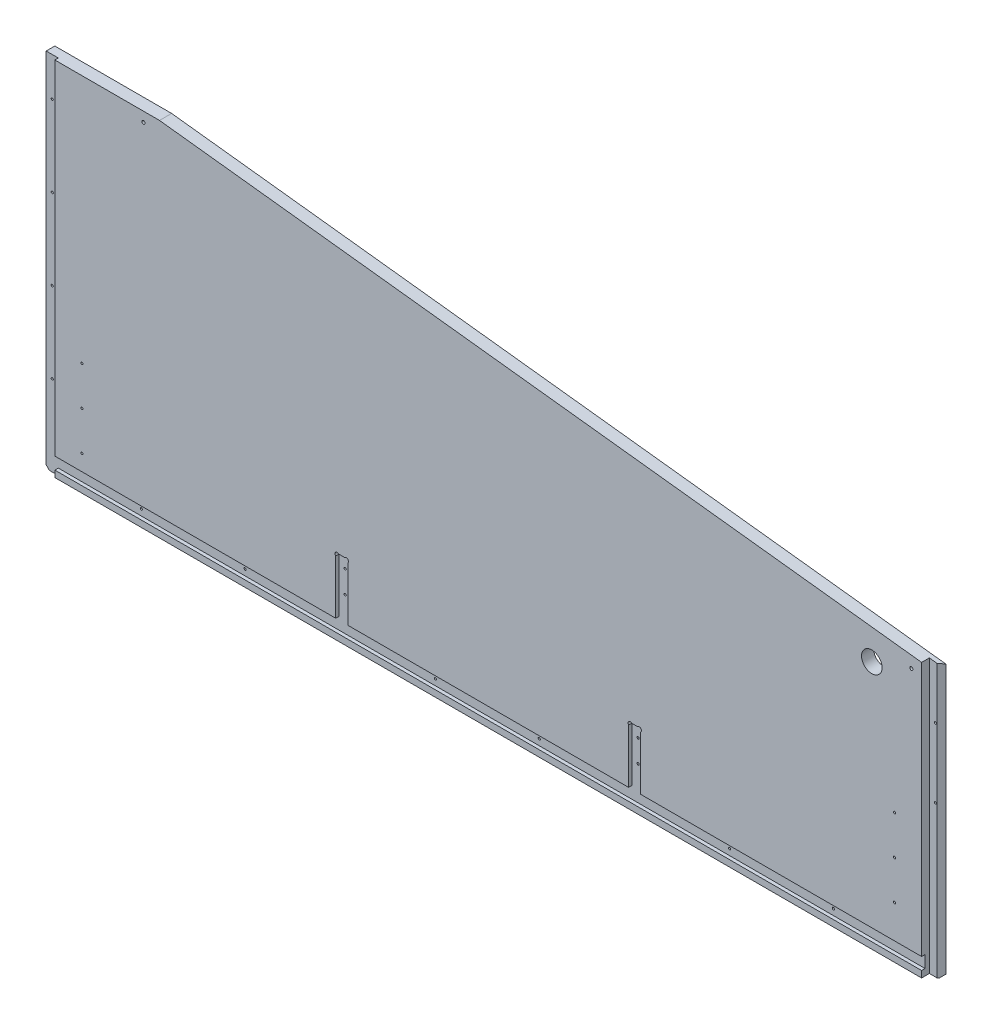
SolidWorks part; units mm, degrees
material "Pine"
ref_plane "Front Plane" through (0, 0, 0) normal (0, 0, 1) x (1, 0, 0)
ref_plane "Top Plane" through (0, 0, 0) normal (0, 1, 0) x (1, 0, 0)
ref_plane "Right Plane" through (0, 0, 0) normal (1, 0, 0) x (0, 0, -1)
sketch "Sketch1" plane through (0, 0, 0) normal (0, 0, 1) x (1, 0, 0)
  line L0 (8932.6508, -5243.5125) -> (10226.1458, -5243.5125)
  line L1 (9086.3208, -4722.0918) -> (10222.9708, -4853.7812)
  line L2 (8914.8708, -6342.0625) -> (10197.5708, -6342.0625)
  line L3 (8914.8708, -5808.6625) -> (10197.5708, -5808.6625)
  line L4 (8919.6333, -5253.0375) -> (10218.2083, -5253.0375)
  line L5 (9134.2633, -4656.1375) -> (9134.2633, -4638.3575)
  line L6 (9091.0833, -4638.3575) -> (9134.2633, -4638.3575)
  line L7 (9091.0833, -4567.2375) -> (9091.0833, -4638.3575)
  line L8 (9134.2633, -4656.1375) -> (9581.3033, -4656.1375)
  line L9 (9091.0833, -4567.2375) -> (9624.4833, -4567.2375)
  line L10 (9581.3033, -4656.1375) -> (9581.3033, -4638.3575)
  line L11 (9581.3033, -4638.3575) -> (9624.4833, -4638.3575)
  line L12 (9624.4833, -4567.2375) -> (9624.4833, -4638.3575)
  line L13 (8932.6508, -5225.7325) -> (9344.9775, -5225.7325)
  line L14 (8932.6508, -5256.2125) -> (8932.6508, -5243.5125)
  line L15 (8911.6958, -5256.2125) -> (8932.6508, -5256.2125)
  line L16 (8914.8708, -4722.0918) -> (9086.3208, -4722.0918)
  line L17 (8911.6958, -4715.5913) -> (8932.6508, -4715.5913)
  line L18 (8914.8708, -6342.0625) -> (8914.8708, -5808.6625)
  line L19 (12082.9917, -4722.0918) -> (10946.3417, -4853.7812)
  line L20 (12236.6617, -5243.5125) -> (10943.1667, -5243.5125)
  line L21 (10951.1042, -5253.0375) -> (12249.6792, -5253.0375)
  line L22 (10838.3917, -5656.2625) -> (11308.2917, -5656.2625)
  line L23 (10838.3917, -5719.7625) -> (11308.2917, -5719.7625)
  line L24 (10838.3917, -5742.5368) -> (11308.2917, -5742.5368)
  line L25 (10806.6417, -6342.0625) -> (11340.0417, -6342.0625)
  line L26 (10803.4667, -6335.7125) -> (11343.2167, -6335.7125)
  line L27 (10803.4667, -6317.9325) -> (11343.2167, -6317.9325)
  line L28 (10943.1667, -5225.7325) -> (11376.4483, -5225.7325)
  line L29 (11506.7292, -4754.5625) -> (10806.6417, -4827.5875)
  line L30 (11506.7292, -4567.2375) -> (11506.7292, -4754.5625)
  line L31 (10806.6417, -4567.2375) -> (10806.6417, -4827.5875)
  line L32 (10806.6417, -4567.2375) -> (11506.7292, -4567.2375)
  line L33 (10235.6708, -6329.3625) -> (10245.1958, -6329.3625)
  line L34 (10245.1958, -6329.3625) -> (10254.7208, -6278.5625)
  line L35 (10302.3458, -6329.3625) -> (10311.8708, -6278.5625)
  line L36 (10302.3458, -6329.3625) -> (10292.8208, -6329.3625)
  line L37 (10245.1958, -5821.3625) -> (10254.7208, -5872.1625)
  line L38 (10235.6708, -5821.3625) -> (10245.1958, -5821.3625)
  line L39 (10292.8208, -5821.3625) -> (10302.3458, -5821.3625)
  line L40 (10302.3458, -5821.3625) -> (10311.8708, -5872.1625)
  line L41 (10235.6708, -5821.3625) -> (10235.6708, -6329.3625)
  line L42 (10254.7208, -5872.1625) -> (10254.7208, -6278.5625)
  line L43 (10311.8708, -5872.1625) -> (10311.8708, -6278.5625)
  line L44 (10292.8208, -5821.3625) -> (10292.8208, -6329.3625)
  line L45 (8932.6508, -5225.7325) -> (8932.6508, -4715.5913)
  line L46 (8911.6958, -4715.5913) -> (8911.6958, -5256.2125)
  line L47 (8914.8708, -5248.275) -> (8914.8708, -4722.0918)
  line L48 (8919.6333, -5253.0375) -> (8914.8708, -5248.275)
  line L49 (8914.8708, -5145.0875) -> (8937.426, -5145.0875)
  line L50 (8914.8708, -5202.2375) -> (8937.426, -5202.2375)
  line L51 (10838.3917, -5656.2625) -> (10838.3917, -5719.7625)
  line L52 (10832.0417, -5736.1868) -> (10856.1717, -5736.1868)
  line L53 (10806.6417, -6342.0625) -> (10806.6417, -5818.7368)
  line L54 (10832.0417, -5649.9125) -> (10856.1717, -5649.9125)
  line L55 (10832.0417, -5726.1125) -> (10856.1717, -5726.1125)
  line L56 (10806.6417, -5818.7368) -> (10833.9015, -5818.7368)
  line L57 (10832.0417, -5806.0442) -> (10851.6815, -5806.0442)
  line L58 (10856.1717, -5801.5541) -> (10856.1717, -5736.1868)
  line L59 (10838.3917, -5814.2467) -> (10838.3917, -5742.5368)
  line L60 (10832.0417, -5806.0442) -> (10832.0417, -5736.1868)
  line L61 (10803.4667, -6317.9325) -> (10803.4667, -6335.7125)
  line L62 (10197.5708, -5808.6625) -> (10197.5708, -6342.0625)
  line L63 (9762.3842, -6348.4125) -> (9762.3842, -5802.3125)
  line L64 (9780.1642, -6348.4125) -> (9762.3842, -6348.4125)
  line L65 (9780.1642, -5802.3125) -> (9780.1642, -6348.4125)
  line L66 (9762.3842, -5802.3125) -> (9780.1642, -5802.3125)
  line L67 (9332.2775, -6348.4125) -> (9332.2775, -5802.3125)
  line L68 (9332.2775, -6348.4125) -> (9350.0575, -6348.4125)
  line L69 (9350.0575, -5802.3125) -> (9350.0575, -6348.4125)
  line L70 (9332.2775, -5802.3125) -> (9350.0575, -5802.3125)
  line L71 (9993.8374, -6061.075) -> (9993.8374, -6045.2418)
  line L72 (9998.5999, -6065.8375) -> (10014.4331, -6065.8375)
  line L73 (9998.5999, -6084.8875) -> (10014.4331, -6084.8875)
  line L74 (9993.8374, -6105.4832) -> (9993.8374, -6089.65)
  line L75 (9974.7874, -6105.4832) -> (9974.7874, -6089.65)
  line L76 (9954.1917, -6084.8875) -> (9970.0249, -6084.8875)
  line L77 (9974.7874, -6061.075) -> (9974.7874, -6045.2418)
  line L78 (9954.1917, -6065.8375) -> (9970.0249, -6065.8375)
  line L79 (10793.9417, -6237.2875) -> (10816.4969, -6237.2875)
  line L80 (10793.9417, -6294.4375) -> (10816.4969, -6294.4375)
  line L81 (10856.1717, -5649.9125) -> (10856.1717, -5726.1125)
  line L82 (10832.0417, -5726.1125) -> (10832.0417, -5649.9125)
  line L83 (10226.1458, -5225.7325) -> (10226.1458, -5243.5125)
  line L84 (10205.1908, -5257.8) -> (10205.1908, -4844.2499)
  line L85 (10230.9083, -4844.2499) -> (10230.9083, -5257.8)
  line L86 (10205.1908, -5257.8) -> (10230.9083, -5257.8)
  line L87 (10205.1908, -4844.2499) -> (10230.9083, -4844.2499)
  line L88 (10946.3417, -5176.8375) -> (10968.8969, -5176.8375)
  line L89 (9349.4676, -5141.9125) -> (9358.2674, -5141.9125)
  line L90 (10946.3417, -5119.6875) -> (10968.8969, -5119.6875)
  line L91 (9929.011, -4660.9635) -> (10066.0807, -4660.9635)
  line L92 (9929.011, -4678.7435) -> (10066.0807, -4678.7435)
  line L93 (10943.1667, -5225.7325) -> (10943.1667, -5243.5125)
  line L94 (10946.3417, -5248.275) -> (10951.1042, -5253.0375)
  line L95 (10946.3417, -5257.8063) -> (10946.3417, -4849.0188)
  line L96 (10964.1217, -5257.8) -> (10964.1217, -4844.2499)
  line L97 (10938.4042, -4844.2499) -> (10938.4042, -5257.8)
  line L98 (10938.4042, -5257.8) -> (10964.1217, -5257.8)
  line L99 (10964.1217, -4844.2499) -> (10938.4042, -4844.2499)
  line L100 (10344.8908, -4560.8875) -> (10369.0208, -4560.8875)
  line L101 (10344.8908, -4560.8875) -> (10369.0208, -4560.8875)
  line L102 (10800.2917, -4560.8875) -> (10824.4217, -4560.8875)
  line L103 (10200.4156, -5119.6875) -> (10222.9708, -5119.6875)
  line L104 (10200.4156, -5176.8375) -> (10222.9708, -5176.8375)
  line L105 (9344.9775, -5146.4026) -> (9344.9775, -5225.7325)
  line L106 (10344.8908, -4560.8875) -> (10344.8908, -4833.9375)
  line L107 (9792.8642, -5225.7325) -> (9792.8642, -5146.4026)
  line L108 (9362.7575, -5225.7325) -> (9775.0842, -5225.7325)
  line L109 (9680.3633, -4761.8396) -> (9680.3633, -4559.9604)
  line L110 (9656.2333, -4559.9604) -> (9680.3633, -4559.9604)
  line L111 (9656.2333, -4761.8396) -> (9680.3633, -4761.8396)
  line L112 (9656.2333, -4761.8396) -> (9656.2333, -4559.9604)
  line L113 (9779.5743, -5141.9125) -> (9788.374, -5141.9125)
  line L114 (10070.5708, -4665.4536) -> (10070.5708, -4674.2534)
  line L115 (9924.5208, -4674.2534) -> (9924.5208, -4665.4536)
  line L116 (12127.4417, -6188.3925) -> (12205.5015, -6188.3925)
  line L117 (12209.9917, -6170.6125) -> (12209.9917, -6183.9024)
  line L118 (9792.8642, -5225.7325) -> (10226.1458, -5225.7325)
  line L119 (9662.5833, -4754.5625) -> (10362.6708, -4827.5875)
  line L120 (9662.5833, -4567.2375) -> (9662.5833, -4754.5625)
  line L121 (10362.6708, -4567.2375) -> (10362.6708, -4827.5875)
  line L122 (9662.5833, -4567.2375) -> (10362.6708, -4567.2375)
  line L123 (10824.4217, -4833.9375) -> (10800.2917, -4833.9375)
  line L124 (10800.2917, -4833.9375) -> (10800.2917, -4560.8875)
  line L125 (10824.4217, -4560.8875) -> (10824.4217, -4833.9375)
  line L126 (10344.8908, -4833.9375) -> (10369.0208, -4833.9375)
  line L127 (10369.0208, -4833.9375) -> (10369.0208, -4560.8875)
  line L128 (10222.9708, -5248.275) -> (10218.2083, -5253.0375)
  line L129 (10222.9708, -5257.8063) -> (10222.9708, -4849.0188)
  line L130 (11734.6544, -5701.375) -> (11739.2301, -5701.375)
  line L131 (9362.7575, -5225.7325) -> (9362.7575, -5146.4026)
  line L132 (9775.0842, -5146.4026) -> (9775.0842, -5225.7325)
  line L133 (11761.3864, -5701.375) -> (11756.8282, -5701.375)
  line L134 (11734.6544, -5693.755) -> (11739.2301, -5693.755)
  line L135 (11761.4039, -5693.755) -> (11756.8282, -5693.755)
  line L136 (11734.6544, -5701.375) -> (11739.2301, -5701.375)
  line L137 (11744.3462, -5721.3024) -> (11744.3462, -5706.4179)
  line L138 (11751.7122, -5721.3024) -> (11751.7122, -5706.4179)
  line L139 (11740.0917, -6170.6125) -> (11740.0917, -6183.9024)
  line L140 (11689.2917, -6188.3925) -> (11822.6417, -6188.3925)
  line L141 (11689.2917, -6348.4093) -> (11689.2917, -6164.2657)
  line L142 (11689.2917, -6164.2657) -> (11746.4417, -6164.2657)
  line L143 (11746.4417, -6164.2657) -> (11746.4417, -6188.3925)
  line L144 (11689.2917, -6164.2657) -> (11746.4417, -6164.2657)
  line L145 (11340.0417, -5818.7368) -> (11340.0417, -6342.0625)
  line L146 (11290.5117, -5726.1125) -> (11314.6417, -5726.1125)
  line L147 (11290.5117, -5649.9125) -> (11290.5117, -5726.1125)
  line L148 (11340.0417, -5818.7368) -> (11312.7818, -5818.7368)
  line L149 (11314.6417, -5806.0442) -> (11295.0018, -5806.0442)
  line L150 (11290.5117, -5801.5541) -> (11290.5117, -5736.1868)
  line L151 (11308.2917, -5814.2467) -> (11308.2917, -5742.5368)
  line L152 (11314.6417, -5806.0442) -> (11314.6417, -5736.1868)
  line L153 (11290.5117, -5736.1868) -> (11314.6417, -5736.1868)
  line L154 (11848.0417, -6267.1325) -> (11962.3417, -6267.1325)
  line L155 (11962.3417, -6267.1325) -> (11962.3417, -6203.6325)
  line L156 (11343.2167, -6317.9325) -> (11343.2167, -6335.7125)
  line L157 (11365.4417, -5656.2625) -> (11365.4417, -5719.7625)
  line L158 (11365.4417, -5656.2625) -> (11479.7417, -5656.2625)
  line L159 (11778.1917, -6071.3937) -> (11802.3217, -6071.3937)
  line L160 (11314.6417, -5726.1125) -> (11314.6417, -5649.9125)
  line L161 (11314.6417, -5649.9125) -> (11290.5117, -5649.9125)
  line L162 (11308.2917, -5719.7625) -> (11308.2917, -5656.2625)
  line L163 (11689.2917, -6348.4093) -> (11713.4217, -6348.4093)
  line L164 (12203.6417, -6164.2657) -> (12260.7917, -6164.2657)
  line L165 (11713.4217, -6348.4093) -> (11713.4217, -6164.2657)
  line L166 (11695.6417, -6342.0625) -> (11695.6417, -6170.6125)
  line L167 (11695.6417, -6048.5337) -> (11699.4517, -6052.3437)
  line L168 (11822.6417, -6292.5325) -> (11822.6417, -6188.3925)
  line L169 (11695.6417, -6342.0625) -> (11695.6417, -6170.6125)
  line L170 (11848.0417, -6203.6325) -> (11962.3417, -6203.6325)
  line L171 (11848.0417, -6203.6325) -> (11848.0417, -6267.1325)
  line L172 (11987.7417, -6267.1325) -> (11987.7417, -6203.6325)
  line L173 (11784.5417, -6077.7437) -> (11784.5417, -6141.2438)
  line L174 (11517.8417, -5656.2625) -> (11632.1417, -5656.2625)
  line L175 (11632.1417, -5656.2625) -> (11632.1417, -5719.7625)
  line L176 (11632.1417, -5719.7625) -> (11517.8417, -5719.7625)
  line L177 (11517.8417, -5719.7625) -> (11517.8417, -5656.2625)
  line L178 (11692.4667, -6028.2137) -> (11692.4667, -6045.9937)
  line L179 (11695.6417, -5979.3188) -> (11718.1969, -5979.3188)
  line L180 (11695.6417, -5922.1687) -> (11718.1969, -5922.1687)
  line L181 (11821.0415, -5722.9375) -> (11821.0415, -5943.6)
  line L182 (11687.7042, -5651.5) -> (11701.9917, -5651.5)
  line L183 (11687.7042, -5651.5) -> (11687.7042, -6055.5251)
  line L184 (11687.7042, -6055.5251) -> (11701.9917, -6055.5251)
  line L185 (11701.9917, -6055.5251) -> (11701.9917, -5651.5)
  line L186 (11695.6417, -6055.2013) -> (11695.6417, -5649.595)
  line L187 (11695.6417, -5656.2625) -> (11695.6417, -6048.5337)
  line L188 (11695.6417, -6170.6125) -> (11740.0917, -6170.6125)
  line L189 (12203.6417, -6164.2657) -> (12203.6417, -6188.3925)
  line L190 (12254.4417, -6342.0625) -> (12254.4417, -6170.6125)
  line L191 (12129.0419, -5943.6) -> (12129.0419, -5722.9375)
  line L192 (12254.4417, -6048.5337) -> (12250.6317, -6052.3437)
  line L193 (12257.6167, -6045.9937) -> (12257.6167, -6028.2137)
  line L194 (12248.0917, -5651.5) -> (12262.3792, -5651.5)
  line L195 (12262.3792, -5651.5) -> (12262.3792, -6055.5251)
  line L196 (12262.3792, -6055.5251) -> (12248.0917, -6055.5251)
  line L197 (12248.0917, -6055.5251) -> (12248.0917, -5651.5)
  line L198 (12254.4417, -6141.2438) -> (12254.4417, -6077.7437)
  line L199 (12236.6617, -6164.2657) -> (12260.7917, -6164.2657)
  line L200 (12102.0417, -6267.1325) -> (11987.7417, -6267.1325)
  line L201 (11330.1865, -6237.2875) -> (11352.7417, -6237.2875)
  line L202 (11330.1865, -6294.4375) -> (11352.7417, -6294.4375)
  line L203 (11474.6617, -5851.8425) -> (11492.4417, -5851.8425)
  line L204 (11474.6617, -5808.6625) -> (11474.6617, -5851.8425)
  line L205 (11403.5417, -5808.6625) -> (11474.6617, -5808.6625)
  line L206 (11492.4417, -5851.8425) -> (11492.4417, -6298.8825)
  line L207 (11403.5417, -6342.0625) -> (11403.5417, -5808.6625)
  line L208 (11474.6617, -6298.8825) -> (11492.4417, -6298.8825)
  line L209 (11474.6617, -6342.0625) -> (11474.6617, -6298.8825)
  line L210 (11403.5417, -6342.0625) -> (11474.6617, -6342.0625)
  line L211 (11619.4417, -5851.8425) -> (11601.6617, -5851.8425)
  line L212 (11601.6617, -5808.6625) -> (11601.6617, -5851.8425)
  line L213 (11530.5417, -5808.6625) -> (11601.6617, -5808.6625)
  line L214 (11619.4417, -5851.8425) -> (11619.4417, -6298.8825)
  line L215 (11530.5417, -6342.0625) -> (11530.5417, -5808.6625)
  line L216 (11619.4417, -6298.8825) -> (11601.6617, -6298.8825)
  line L217 (11601.6617, -6342.0625) -> (11601.6617, -6298.8825)
  line L218 (11530.5417, -6342.0625) -> (11601.6617, -6342.0625)
  line L219 (11479.7417, -5719.7625) -> (11479.7417, -5656.2625)
  line L220 (11365.4417, -5719.7625) -> (11479.7417, -5719.7625)
  line L221 (11778.1917, -6147.5937) -> (11802.3217, -6147.5937)
  line L222 (11802.3217, -6071.3937) -> (11802.3217, -6147.5937)
  line L223 (11778.1917, -6147.5937) -> (11778.1917, -6071.3937)
  line L224 (12254.4417, -5922.1687) -> (12231.8865, -5922.1687)
  line L225 (12254.4417, -5979.3188) -> (12231.8865, -5979.3188)
  line L226 (12254.4417, -6055.2013) -> (12254.4417, -5649.595)
  line L227 (12254.4417, -6048.5337) -> (12254.4417, -5656.2625)
  line L228 (11841.6917, -5702.2873) -> (12108.3917, -5702.2873)
  line L229 (11822.6417, -6292.5325) -> (12127.4417, -6292.5325)
  line L230 (12127.4417, -6292.5325) -> (12127.4417, -6188.3925)
  line L231 (12254.4417, -6170.6125) -> (12209.9917, -6170.6125)
  line L232 (11695.6417, -6342.0625) -> (12254.4417, -6342.0625)
  line L233 (12236.6617, -6348.4093) -> (12260.7917, -6348.4093)
  line L234 (12260.7917, -6348.4093) -> (12260.7917, -6164.2657)
  line L235 (12236.6617, -6348.4093) -> (12236.6617, -6164.2657)
  line L236 (12102.0417, -6203.6325) -> (12102.0417, -6267.1325)
  line L237 (11987.7417, -6203.6325) -> (12102.0417, -6203.6325)
  line L238 (12236.6617, -6147.5937) -> (12236.6617, -6071.3937)
  line L239 (12203.6417, -6188.3925) -> (12260.7917, -6188.3925)
  line L240 (11098.7417, -4665.4536) -> (11098.7417, -4674.2534)
  line L241 (11394.2283, -5146.4026) -> (11394.2283, -5225.7325)
  line L242 (11376.4483, -5225.7325) -> (11376.4483, -5146.4026)
  line L243 (11394.2283, -5225.7325) -> (11806.555, -5225.7325)
  line L244 (11841.6917, -5964.2502) -> (12108.3917, -5964.2502)
  line L245 (12236.6617, -6147.5937) -> (12260.7917, -6147.5937)
  line L246 (12236.6617, -5256.2125) -> (12236.6617, -5243.5125)
  line L247 (12260.7917, -6147.5937) -> (12260.7917, -6071.3937)
  line L248 (12260.7917, -6071.3937) -> (12236.6617, -6071.3937)
  line L249 (12254.4417, -6077.7437) -> (11784.5417, -6077.7437)
  line L250 (11784.5417, -6141.2438) -> (12254.4417, -6141.2438)
  line L252 (12254.4417, -5656.2625) -> (11695.6417, -5656.2625)
  line L253 (11699.4517, -6052.3437) -> (12250.6317, -6052.3437)
  line L254 (11692.4667, -6045.9937) -> (12257.6167, -6045.9937)
  line L255 (11692.4667, -6028.2137) -> (12257.6167, -6028.2137)
  line L256 (11824.335, -5146.4026) -> (11824.335, -5225.7325)
  line L257 (11811.0451, -5141.9125) -> (11819.8449, -5141.9125)
  line L258 (11244.7917, -4674.2534) -> (11244.7917, -4665.4536)
  line L259 (11806.555, -5225.7325) -> (11806.555, -5146.4026)
  line L260 (11488.9492, -4761.8396) -> (11488.9492, -4559.9604)
  line L261 (11488.9492, -4559.9604) -> (11513.0792, -4559.9604)
  line L262 (11488.9492, -4761.8396) -> (11513.0792, -4761.8396)
  line L263 (11513.0792, -4761.8396) -> (11513.0792, -4559.9604)
  line L264 (11240.3015, -4660.9635) -> (11103.2318, -4660.9635)
  line L265 (11103.2318, -4678.7435) -> (11240.3015, -4678.7435)
  line L266 (12236.6617, -5225.7325) -> (12236.6617, -4715.5913)
  line L267 (12257.6167, -4715.5913) -> (12257.6167, -5256.2125)
  line L268 (12254.4417, -5248.275) -> (12254.4417, -4722.0918)
  line L269 (12236.6617, -5225.7325) -> (11824.335, -5225.7325)
  line L270 (12035.0492, -4656.1375) -> (12035.0492, -4638.3575)
  line L271 (12078.2292, -4638.3575) -> (12035.0492, -4638.3575)
  line L272 (12078.2292, -4567.2375) -> (12078.2292, -4638.3575)
  line L273 (12035.0492, -4656.1375) -> (11588.0092, -4656.1375)
  line L274 (11544.8292, -4567.2375) -> (12078.2292, -4567.2375)
  line L275 (11588.0092, -4656.1375) -> (11588.0092, -4638.3575)
  line L276 (11544.8292, -4638.3575) -> (11588.0092, -4638.3575)
  line L277 (11544.8292, -4567.2375) -> (11544.8292, -4638.3575)
  line L278 (12249.6792, -5253.0375) -> (12254.4417, -5248.275)
  line L280 (12257.6167, -5256.2125) -> (12236.6617, -5256.2125)
  line L281 (12231.8865, -5145.0875) -> (12254.4417, -5145.0875)
  line L282 (12231.8865, -5202.2375) -> (12254.4417, -5202.2375)
  line L283 (12236.6617, -4715.5913) -> (12257.6167, -4715.5913)
  line L284 (12082.9917, -4722.0918) -> (12254.4417, -4722.0918)
  line L285 (11380.9385, -5141.9125) -> (11389.7382, -5141.9125)
  circle A0 centre (8923.7608, -4778.9042) radius 1.5875
  circle A1 centre (9062.6598, -4736.3765) radius 2.3685
  circle A2 centre (9051.3958, -6281.7375) radius 22.225
  circle A3 centre (9083.1458, -6249.9875) radius 1.5875
  circle A4 centre (9083.1458, -6313.4875) radius 1.5875
  circle A5 centre (9019.6458, -6249.9875) radius 1.5875
  circle A6 centre (9019.6458, -6313.4875) radius 1.5875
  circle A7 centre (8972.3383, -5202.2375) radius 1.5875
  circle A8 centre (8923.7608, -5015.9708) radius 1.5875
  circle A9 centre (8923.7608, -5134.5042) radius 1.5875
  circle A10 centre (9054.5708, -5234.6225) radius 1.5875
  circle A11 centre (8923.7608, -4897.4375) radius 1.5875
  circle A12 centre (8972.3383, -5087.9375) radius 1.5875
  circle A13 centre (8972.3383, -5145.0875) radius 1.5875
  circle A14 centre (10847.2817, -5668.9625) radius 1.5875
  circle A15 centre (10847.2817, -5707.0625) radius 1.5875
  circle A16 centre (10847.2817, -5755.2368) radius 1.5875
  circle A17 centre (10851.4092, -6237.2875) radius 1.5875
  circle A18 centre (10851.4092, -6294.4375) radius 1.5875
  circle A19 centre (10847.2817, -5793.3442) radius 1.5875
  arc A20 (10833.9015, -5818.7368) -> (10838.3917, -5814.2467) centre (10836.1466, -5816.4918) ccw
  arc A21 (10851.6815, -5806.0442) -> (10856.1717, -5801.5541) centre (10853.9266, -5803.7992) ccw
  circle A22 centre (10882.8417, -6040.4375) radius 1.5875
  circle A23 centre (10882.8417, -6218.2375) radius 1.5875
  circle A24 centre (10882.8417, -5862.6375) radius 1.5875
  circle A25 centre (10908.2417, -6326.8225) radius 1.5875
  circle A26 centre (10908.2417, -6326.8225) radius 1.5875
  circle A27 centre (10851.4092, -6180.1375) radius 1.5875
  circle A28 centre (10815.5317, -4783.4231) radius 1.5875
  circle A29 centre (10815.5317, -4696.9488) radius 1.5875
  circle A30 centre (10815.5317, -4610.4746) radius 1.5875
  circle A31 centre (10979.1323, -4867.0082) radius 2.3685
  circle A32 centre (10190.1802, -4867.0082) radius 2.3685
  circle A33 centre (10955.2317, -4929.9812) radius 1.5875
  circle A34 centre (10955.2317, -5031.5812) radius 1.5875
  circle A35 centre (10214.0808, -4929.9812) radius 1.5875
  circle A36 centre (10214.0808, -5031.5812) radius 1.5875
  circle A37 centre (9341.1675, -6265.8625) radius 1.5875
  circle A38 centre (9771.2742, -5884.8625) radius 1.5875
  circle A39 centre (9771.2742, -6138.8625) radius 1.5875
  circle A40 centre (9771.2742, -6011.8625) radius 1.5875
  arc A41 (10036.2287, -6113.8083) -> (10051.3426, -6111.6033) centre (10042.9639, -6107.0732) ccw
  arc A42 (10051.3426, -6111.6033) -> (10051.3426, -6039.1217) centre (9984.3124, -6075.3625) ccw
  arc A43 (10051.3426, -6039.1217) -> (10036.2287, -6036.9167) centre (10042.9639, -6043.6518) ccw
  arc A44 (10034.5851, -6102.5431) -> (10034.5851, -6048.1819) centre (9984.3124, -6075.3625) ccw
  arc A45 (10034.5851, -6102.5431) -> (10036.2287, -6113.8083) centre (10042.9639, -6107.0732) ccw
  arc A46 (10036.2287, -6036.9167) -> (10034.5851, -6048.1819) centre (10042.9639, -6043.6518) ccw
  arc A47 (9945.8666, -6127.2787) -> (9948.0717, -6142.3927) centre (9952.6018, -6134.0139) ccw
  arc A48 (9948.0717, -6142.3927) -> (10020.5532, -6142.3927) centre (9984.3124, -6075.3625) ccw
  arc A49 (10020.5532, -6142.3927) -> (10022.7583, -6127.2787) centre (10016.0231, -6134.0139) ccw
  arc A50 (9957.1319, -6125.6352) -> (10011.493, -6125.6352) centre (9984.3124, -6075.3625) ccw
  arc A51 (9957.1319, -6125.6352) -> (9945.8666, -6127.2787) centre (9952.6018, -6134.0139) ccw
  arc A52 (10022.7583, -6127.2787) -> (10011.493, -6125.6352) centre (10016.0231, -6134.0139) ccw
  arc A53 (9932.3962, -6036.9167) -> (9917.2822, -6039.1217) centre (9925.661, -6043.6518) ccw
  arc A54 (9917.2822, -6039.1217) -> (9917.2822, -6111.6033) centre (9984.3124, -6075.3625) ccw
  arc A55 (9917.2822, -6111.6033) -> (9932.3962, -6113.8083) centre (9925.661, -6107.0732) ccw
  arc A56 (9934.0398, -6048.1819) -> (9934.0398, -6102.5431) centre (9984.3124, -6075.3625) ccw
  arc A57 (9934.0398, -6048.1819) -> (9932.3962, -6036.9167) centre (9925.661, -6043.6518) ccw
  arc A58 (9932.3962, -6113.8083) -> (9934.0398, -6102.5431) centre (9925.661, -6107.0732) ccw
  arc A59 (9945.8666, -6023.4463) -> (9957.1319, -6025.0898) centre (9952.6018, -6016.7111) ccw
  arc A60 (10011.493, -6025.0898) -> (10022.7583, -6023.4463) centre (10016.0231, -6016.7111) ccw
  arc A61 (10011.493, -6025.0898) -> (9957.1319, -6025.0898) centre (9984.3124, -6075.3625) ccw
  arc A62 (9948.0717, -6008.3323) -> (9945.8666, -6023.4463) centre (9952.6018, -6016.7111) ccw
  arc A63 (10020.5532, -6008.3323) -> (9948.0717, -6008.3323) centre (9984.3124, -6075.3625) ccw
  arc A64 (10022.7583, -6023.4463) -> (10020.5532, -6008.3323) centre (10016.0231, -6016.7111) ccw
  arc A65 (10005.0943, -6187.7574) -> (10096.7073, -6096.1443) centre (9984.3124, -6075.3625) ccw
  arc A66 (9993.8374, -6178.3911) -> (10005.0943, -6187.7574) centre (10003.3624, -6178.3911) ccw
  arc A67 (10001.6306, -6169.0249) -> (10077.9748, -6092.6807) centre (9984.3124, -6075.3625) ccw
  arc A68 (10087.3411, -6084.8875) -> (10077.9748, -6092.6807) centre (10087.3411, -6094.4125) ccw
  arc A69 (10001.6306, -6169.0249) -> (9993.8374, -6178.3911) centre (10003.3624, -6178.3911) ccw
  arc A70 (9963.5306, -6187.7574) -> (9974.7874, -6178.3911) centre (9965.2624, -6178.3911) ccw
  arc A71 (9871.9176, -6096.1443) -> (9963.5306, -6187.7574) centre (9984.3124, -6075.3625) ccw
  arc A72 (9881.2838, -6084.8875) -> (9871.9176, -6096.1443) centre (9881.2838, -6094.4125) ccw
  arc A73 (9890.65, -6092.6807) -> (9966.9943, -6169.0249) centre (9984.3124, -6075.3625) ccw
  arc A74 (9974.7874, -6178.3911) -> (9966.9943, -6169.0249) centre (9965.2624, -6178.3911) ccw
  arc A75 (9890.65, -6092.6807) -> (9881.2838, -6084.8875) centre (9881.2838, -6094.4125) ccw
  arc A76 (9871.9176, -6054.5807) -> (9881.2838, -6065.8375) centre (9881.2838, -6056.3125) ccw
  arc A77 (9963.5306, -5962.9676) -> (9871.9176, -6054.5807) centre (9984.3124, -6075.3625) ccw
  arc A78 (9974.7874, -5972.3339) -> (9963.5306, -5962.9676) centre (9965.2624, -5972.3339) ccw
  arc A79 (9966.9943, -5981.7001) -> (9890.65, -6058.0443) centre (9984.3124, -6075.3625) ccw
  arc A80 (9881.2838, -6065.8375) -> (9890.65, -6058.0443) centre (9881.2838, -6056.3125) ccw
  arc A81 (9966.9943, -5981.7001) -> (9974.7874, -5972.3339) centre (9965.2624, -5972.3339) ccw
  arc A82 (10077.9748, -6058.0443) -> (10087.3411, -6065.8375) centre (10087.3411, -6056.3125) ccw
  arc A83 (9993.8374, -5972.3339) -> (10001.6306, -5981.7001) centre (10003.3624, -5972.3339) ccw
  arc A84 (10077.9748, -6058.0443) -> (10001.6306, -5981.7001) centre (9984.3124, -6075.3625) ccw
  arc A85 (10087.3411, -6065.8375) -> (10096.7073, -6054.5807) centre (10087.3411, -6056.3125) ccw
  arc A86 (10096.7073, -6054.5807) -> (10005.0943, -5962.9676) centre (9984.3124, -6075.3625) ccw
  arc A87 (10005.0943, -5962.9676) -> (9993.8374, -5972.3339) centre (10003.3624, -5972.3339) ccw
  arc A88 (10014.4331, -6065.8375) -> (10018.7361, -6059.0339) centre (10014.4331, -6061.075) ccw
  arc A89 (10018.7361, -6059.0339) -> (10000.641, -6040.9388) centre (9984.3124, -6075.3625) ccw
  arc A90 (10000.641, -6040.9388) -> (9993.8374, -6045.2418) centre (9998.5999, -6045.2418) ccw
  arc A91 (9993.8374, -6061.075) -> (9998.5999, -6065.8375) centre (9998.5999, -6061.075) ccw
  arc A92 (9993.8374, -6105.4832) -> (10000.641, -6109.7862) centre (9998.5999, -6105.4832) ccw
  arc A93 (10000.641, -6109.7862) -> (10018.7361, -6091.6911) centre (9984.3124, -6075.3625) ccw
  arc A94 (10018.7361, -6091.6911) -> (10014.4331, -6084.8875) centre (10014.4331, -6089.65) ccw
  arc A95 (9998.5999, -6084.8875) -> (9993.8374, -6089.65) centre (9998.5999, -6089.65) ccw
  arc A96 (9954.1917, -6084.8875) -> (9949.8888, -6091.6911) centre (9954.1917, -6089.65) ccw
  arc A97 (9949.8888, -6091.6911) -> (9967.9839, -6109.7862) centre (9984.3124, -6075.3625) ccw
  arc A98 (9967.9839, -6109.7862) -> (9974.7874, -6105.4832) centre (9970.0249, -6105.4832) ccw
  arc A99 (9974.7874, -6089.65) -> (9970.0249, -6084.8875) centre (9970.0249, -6089.65) ccw
  arc A100 (9970.0249, -6065.8375) -> (9974.7874, -6061.075) centre (9970.0249, -6061.075) ccw
  arc A101 (9949.8888, -6059.0339) -> (9954.1917, -6065.8375) centre (9954.1917, -6061.075) ccw
  arc A102 (9967.9839, -6040.9388) -> (9949.8888, -6059.0339) centre (9984.3124, -6075.3625) ccw
  arc A103 (9974.7874, -6045.2418) -> (9967.9839, -6040.9388) centre (9970.0249, -6045.2418) ccw
  arc A104 (10096.7073, -6096.1443) -> (10087.3411, -6084.8875) centre (10087.3411, -6094.4125) ccw
  circle A105 centre (9771.2742, -6265.8625) radius 1.5875
  circle A106 centre (9341.1675, -5884.8625) radius 1.5875
  circle A107 centre (9341.1675, -6138.8625) radius 1.5875
  circle A108 centre (9341.1675, -6011.8625) radius 1.5875
  circle A109 centre (11037.2315, -4887.5494) radius 15.0812
  arc A110 (9349.4676, -5141.9125) -> (9344.9775, -5146.4026) centre (9347.2226, -5144.1576) ccw
  arc A111 (9362.7575, -5146.4026) -> (9358.2674, -5141.9125) centre (9360.5124, -5144.1576) ccw
  circle A112 centre (9946.7458, -4669.8535) radius 1.5875
  arc A113 (9924.5208, -4674.2534) -> (9929.011, -4678.7435) centre (9926.7659, -4676.4984) ccw
  circle A114 centre (11003.8092, -5176.8375) radius 1.5875
  circle A115 centre (11003.8092, -5119.6875) radius 1.5875
  circle A116 centre (10353.7808, -4696.9488) radius 1.5875
  circle A117 centre (10353.7808, -4610.4746) radius 1.5875
  circle A118 centre (10353.7808, -4783.4231) radius 1.5875
  circle A119 centre (11003.8092, -5062.5375) radius 1.5875
  circle A120 centre (9353.8675, -5160.9625) radius 1.5875
  circle A121 centre (9638.7708, -5234.6225) radius 1.5875
  circle A122 centre (9671.4733, -4724.1144) radius 1.5875
  circle A123 centre (9671.4733, -4661.3637) radius 1.5875
  circle A124 centre (9671.4733, -4598.6129) radius 1.5875
  arc A125 (9792.8642, -5146.4026) -> (9788.374, -5141.9125) centre (9790.6191, -5144.1576) ccw
  arc A126 (9779.5743, -5141.9125) -> (9775.0842, -5146.4026) centre (9777.3292, -5144.1576) ccw
  circle A127 centre (10048.3458, -4669.8535) radius 1.5875
  arc A128 (10070.5708, -4665.4536) -> (10066.0807, -4660.9635) centre (10068.3258, -4663.2086) ccw
  arc A129 (10066.0807, -4678.7435) -> (10070.5708, -4674.2534) centre (10068.3258, -4676.4984) ccw
  circle A130 centre (9997.5458, -4669.8535) radius 1.5875
  arc A131 (9929.011, -4660.9635) -> (9924.5208, -4665.4536) centre (9926.7659, -4663.2086) ccw
  circle A132 centre (10132.081, -4887.5494) radius 15.0812
  circle A133 centre (10165.5033, -5176.8375) radius 1.5875
  circle A134 centre (10165.5033, -5119.6875) radius 1.5875
  circle A135 centre (9486.3708, -5234.6225) radius 1.5875
  circle A136 centre (10165.5033, -5062.5375) radius 1.5875
  circle A137 centre (9206.9708, -5234.6225) radius 1.5875
  circle A138 centre (10070.5708, -5234.6225) radius 1.5875
  circle A139 centre (9918.1708, -5234.6225) radius 1.5875
  circle A140 centre (9783.9742, -5160.9625) radius 1.5875
  circle A141 centre (9783.9742, -5193.9825) radius 1.5875
  circle A142 centre (9353.8675, -5193.9825) radius 1.5875
  circle A143 centre (11073.3417, -6326.8225) radius 1.5875
  circle A144 centre (11073.3417, -6326.8225) radius 1.5875
  circle A145 centre (11295.2742, -6180.1375) radius 1.5875
  circle A146 centre (11295.2742, -6294.4375) radius 1.5875
  circle A147 centre (11295.2742, -6237.2875) radius 1.5875
  circle A148 centre (11975.0417, -5692.775) radius 3.4925
  circle A149 centre (11263.8417, -5862.6375) radius 1.5875
  arc A150 (11739.2301, -5701.375) -> (11744.3462, -5706.4179) centre (11748.0292, -5697.565) ccw
  arc A151 (11751.7122, -5706.4179) -> (11756.8282, -5701.375) centre (11748.0292, -5697.565) ccw
  arc A152 (11744.3462, -5721.3024) -> (11751.7122, -5721.3024) centre (11748.0292, -5725.505) ccw
  arc A153 (11734.6544, -5693.755) -> (11724.9787, -5697.565) centre (11730.5667, -5697.565) ccw
  arc A154 (11756.8282, -5693.755) -> (11739.2301, -5693.755) centre (11748.0292, -5697.565) ccw
  arc A155 (11724.9787, -5697.565) -> (11734.6544, -5701.375) centre (11730.5667, -5697.565) ccw
  arc A156 (11761.3864, -5701.375) -> (11771.0797, -5697.565) centre (11765.4842, -5697.565) ccw
  arc A157 (11771.0797, -5697.565) -> (11761.4039, -5693.755) centre (11765.4917, -5697.565) ccw
  arc A158 (11740.0917, -6183.9024) -> (11744.5818, -6188.3925) centre (11742.3367, -6186.1474) ccw
  arc A159 (12205.5015, -6188.3925) -> (12209.9917, -6183.9024) centre (12207.7466, -6186.1474) ccw
  circle A160 centre (11299.4017, -5793.3442) radius 1.5875
  arc A161 (11308.2917, -5814.2467) -> (11312.7818, -5818.7368) centre (11310.5367, -5816.4918) ccw
  arc A162 (11290.5117, -5801.5541) -> (11295.0018, -5806.0442) centre (11292.7567, -5803.7992) ccw
  circle A163 centre (11704.5317, -6314.149) radius 1.5875
  circle A164 centre (11748.9817, -6208.7125) radius 1.5875
  circle A165 centre (11263.8417, -6218.2375) radius 1.5875
  circle A166 centre (11263.8417, -6040.4375) radius 1.5875
  circle A167 centre (11238.4417, -6326.8225) radius 1.5875
  circle A168 centre (11238.4417, -6326.8225) radius 1.5875
  circle A169 centre (11299.4017, -5668.9625) radius 1.5875
  circle A170 centre (11299.4017, -5707.0625) radius 1.5875
  circle A171 centre (11726.7567, -6179.5025) radius 1.5875
  circle A172 centre (11704.5317, -6199.3198) radius 1.5875
  circle A173 centre (11748.9817, -6272.2125) radius 1.5875
  circle A174 centre (11704.5317, -6256.7344) radius 1.5875
  circle A175 centre (11299.4017, -5755.2368) radius 1.5875
  circle A176 centre (11913.4467, -6301.4225) radius 1.5875
  circle A177 centre (11790.2567, -6301.4225) radius 1.5875
  circle A178 centre (11793.4317, -6128.5437) radius 1.5875
  circle A179 centre (11753.1092, -5865.0188) radius 1.5875
  circle A180 centre (11809.9417, -6037.1038) radius 1.5875
  circle A181 centre (11809.9417, -6037.1038) radius 1.5875
  circle A182 centre (11753.1092, -5922.1687) radius 1.5875
  circle A183 centre (11975.0417, -5973.7625) radius 3.4925
  circle A184 centre (11975.0417, -6037.1038) radius 1.5875
  circle A185 centre (11753.1092, -5979.3188) radius 1.5875
  circle A186 centre (11975.0417, -6037.1038) radius 1.5875
  arc A187 (11841.6917, -5702.2873) -> (11821.0415, -5722.9375) centre (11841.6917, -5722.9375) ccw
  circle A188 centre (11811.5292, -5833.2687) radius 3.4925
  arc A189 (11821.0415, -5943.6) -> (11841.6917, -5964.2502) centre (11841.6917, -5943.6) ccw
  circle A190 centre (12196.9742, -5865.0188) radius 1.5875
  arc A191 (12129.0419, -5722.9375) -> (12108.3917, -5702.2873) centre (12108.3917, -5722.9375) ccw
  circle A192 centre (12036.6367, -6301.4225) radius 1.5875
  circle A193 centre (12159.8267, -6301.4225) radius 1.5875
  circle A194 centre (12138.5542, -5833.2687) radius 3.4925
  circle A195 centre (12197.2917, -5761.0375) radius 15.0812
  circle A196 centre (11793.4317, -6090.4437) radius 1.5875
  circle A197 centre (12196.9742, -5922.1687) radius 1.5875
  arc A198 (12108.3917, -5964.2502) -> (12129.0419, -5943.6) centre (12108.3917, -5943.6) ccw
  circle A199 centre (12196.9742, -5979.3188) radius 1.5875
  circle A200 centre (12201.1017, -6272.2125) radius 1.5875
  circle A201 centre (12245.5517, -6314.149) radius 1.5875
  circle A202 centre (12245.5517, -6256.7344) radius 1.5875
  circle A203 centre (12201.1017, -6208.7125) radius 1.5875
  circle A204 centre (12223.3267, -6179.5025) radius 1.5875
  circle A205 centre (12245.5517, -6199.3198) radius 1.5875
  circle A206 centre (11171.7667, -4669.8535) radius 1.5875
  circle A207 centre (11222.5667, -4669.8535) radius 1.5875
  arc A208 (11240.3015, -4678.7435) -> (11244.7917, -4674.2534) centre (11242.5466, -4676.4984) ccw
  circle A209 centre (11385.3383, -5193.9825) radius 1.5875
  circle A210 centre (12106.6527, -4736.3765) radius 2.3685
  circle A211 centre (12140.1417, -6037.1038) radius 1.5875
  circle A212 centre (12140.1417, -6037.1038) radius 1.5875
  circle A213 centre (12245.5517, -6090.4437) radius 1.5875
  circle A214 centre (12245.5517, -6128.5437) radius 1.5875
  circle A215 centre (11385.3383, -5160.9625) radius 1.5875
  arc A216 (11824.335, -5146.4026) -> (11819.8449, -5141.9125) centre (11822.0899, -5144.1576) ccw
  arc A217 (11811.0451, -5141.9125) -> (11806.555, -5146.4026) centre (11808.8001, -5144.1576) ccw
  circle A218 centre (11815.445, -5193.9825) radius 1.5875
  circle A219 centre (11815.445, -5160.9625) radius 1.5875
  circle A220 centre (11530.5417, -5234.6225) radius 1.5875
  circle A221 centre (11962.3417, -5234.6225) radius 1.5875
  arc A222 (11244.7917, -4665.4536) -> (11240.3015, -4660.9635) centre (11242.5466, -4663.2086) ccw
  circle A223 centre (11682.9417, -5234.6225) radius 1.5875
  circle A224 centre (11497.8392, -4724.1144) radius 1.5875
  circle A225 centre (11497.8392, -4661.3637) radius 1.5875
  circle A226 centre (11497.8392, -4598.6129) radius 1.5875
  circle A227 centre (11120.9667, -4669.8535) radius 1.5875
  arc A228 (11103.2318, -4660.9635) -> (11098.7417, -4665.4536) centre (11100.9867, -4663.2086) ccw
  arc A229 (11098.7417, -4674.2534) -> (11103.2318, -4678.7435) centre (11100.9867, -4676.4984) ccw
  circle A230 centre (12196.9742, -5202.2375) radius 1.5875
  circle A231 centre (12245.5517, -5015.9708) radius 1.5875
  circle A232 centre (12245.5517, -5134.5042) radius 1.5875
  circle A233 centre (12114.7417, -5234.6225) radius 1.5875
  circle A234 centre (12245.5517, -4897.4375) radius 1.5875
  circle A235 centre (12245.5517, -4778.9042) radius 1.5875
  circle A236 centre (12196.9742, -5087.9375) radius 1.5875
  circle A237 centre (12196.9742, -5145.0875) radius 1.5875
  circle A238 centre (11098.7417, -5234.6225) radius 1.5875
  circle A239 centre (11251.1417, -5234.6225) radius 1.5875
  arc A240 (11380.9385, -5141.9125) -> (11376.4483, -5146.4026) centre (11378.6934, -5144.1576) ccw
  arc A241 (11394.2283, -5146.4026) -> (11389.7382, -5141.9125) centre (11391.9833, -5144.1576) ccw
sketch "Sketch7" plane through (0, 0, 0) normal (0, 0, 1) x (1, 0, 0)
  line L0 (9086.3208, -4722.0918) -> (10222.9708, -4853.7812)
  line L1 (10222.9708, -4853.7812) -> (10222.9708, -5248.275)
  line L2 (10222.9708, -5248.275) -> (10218.2083, -5253.0375)
  line L3 (10218.2083, -5253.0375) -> (8919.6333, -5253.0375)
  line L4 (8919.6333, -5253.0375) -> (8914.8708, -5248.275)
  line L5 (8914.8708, -5248.275) -> (8914.8708, -4722.0918)
  line L6 (8914.8708, -4722.0918) -> (9086.3208, -4722.0918)
extrude "Extrude2" add sketch "Sketch7" against normal blind 17.78
sketch "Sketch8" plane through (0, 0, 0) normal (0, 0, 1) x (1, 0, 0)
  line L0 (8932.6508, -4722.0918) -> (8914.8708, -4722.0918)
  line L1 (8914.8708, -4722.0918) -> (8914.8708, -5253.0375)
  line L2 (8914.8708, -5253.0375) -> (8932.6508, -5253.0375)
  line L3 (8932.6508, -5253.0375) -> (8932.6508, -5243.5125)
  line L4 (8932.6508, -5243.5125) -> (10222.9708, -5243.5125)
  line L5 (10222.9708, -5243.5125) -> (10222.9708, -5225.7325)
  line L6 (10222.9708, -5225.7325) -> (9792.8642, -5225.7325)
  line L7 (9792.8642, -5225.7325) -> (9792.8642, -5141.9125)
  line L8 (10222.9708, -5248.275) -> (10222.9708, -4853.7812) construction
  line L9 (9792.8642, -5141.9125) -> (9775.0842, -5141.9125)
  line L11 (9775.0842, -5141.9125) -> (9775.0842, -5225.7325)
  line L12 (9775.0842, -5225.7325) -> (9362.7575, -5225.7325)
  line L13 (9362.7575, -5225.7325) -> (9362.7575, -5141.9125)
  line L15 (9362.7575, -5141.9125) -> (9344.9775, -5141.9125)
  line L17 (9344.9775, -5141.9125) -> (9344.9775, -5225.7325)
  line L18 (9344.9775, -5225.7325) -> (8932.6508, -5225.7325)
  line L19 (8932.6508, -5225.7325) -> (8932.6508, -4722.0918)
  line L20 (9086.3208, -4722.0918) -> (8914.8708, -4722.0918) construction
  line L21 (8919.6333, -5253.0375) -> (10218.2083, -5253.0375) construction
  dimension "D1" = 17.78
  dimension "D2" = 17.78
  dimension "D3" = 17.78
  dimension "D4" = 17.78
  dimension "D5" = 17.78
extrude "Cut-Extrude3" cut sketch "Sketch8" against normal blind 5.08
sketch "Sketch9" plane through (0, 0, 0) normal (0, 0, 1) x (1, 0, 0)
  line L0 (9344.9775, -5141.9125) -> (9347.2226, -5144.1576) construction
  line L1 (9344.9775, -5141.9125) -> (9344.9775, -5225.7325) construction
  line L2 (9362.7575, -5141.9125) -> (9360.5124, -5144.1576) construction
  line L3 (9362.7575, -5225.7325) -> (9362.7575, -5141.9125) construction
  line L4 (9775.0842, -5141.9125) -> (9777.3292, -5144.1576) construction
  line L5 (9792.8642, -5141.9125) -> (9790.6191, -5144.1576) construction
  line L6 (9775.0842, -5141.9125) -> (9775.0842, -5225.7325) construction
  line L8 (9792.8642, -5225.7325) -> (9792.8642, -5141.9125) construction
  circle A0 centre (9347.2226, -5144.1576) radius 3.302
  circle A1 centre (9360.5124, -5144.1576) radius 3.175
  circle A2 centre (9777.3292, -5144.1576) radius 3.175
  circle A3 centre (9790.6191, -5144.1576) radius 3.175
  dimension "D1" = 45
  dimension "D2" = 3.175
  dimension "D3" = 45
  dimension "D4" = 3.175
  dimension "D5" = 45
  dimension "D6" = 3.175
  dimension "D7" = 3.175
  dimension "D8" = 45
extrude "Cut-Extrude4" cut sketch "Sketch9" against normal blind 5.08
sketch "Sketch10" plane through (0, 0, 0) normal (0, 0, 1) x (1, 0, 0)
  circle A0 centre (10132.081, -4887.5494) radius 15.0813
  circle A1 centre (9062.6598, -4736.3765) radius 2.3686
  circle A2 centre (8923.7608, -4778.9042) radius 1.5875
  circle A3 centre (8923.7608, -4897.4375) radius 1.5875
  circle A4 centre (8923.7608, -5015.9708) radius 1.5875
  circle A5 centre (8923.7608, -5134.5042) radius 1.5875
  circle A6 centre (9054.5708, -5234.6225) radius 1.5875
  circle A7 centre (9206.9708, -5234.6225) radius 1.5875
  circle A8 centre (9353.8675, -5193.9825) radius 1.5875
  circle A9 centre (9353.8675, -5160.9625) radius 1.5875
  circle A10 centre (9486.3708, -5234.6225) radius 1.5875
  circle A11 centre (9638.7708, -5234.6225) radius 1.5875
  circle A12 centre (9783.9742, -5193.9825) radius 1.5875
  circle A13 centre (9783.9742, -5160.9625) radius 1.5875
  circle A14 centre (9918.1708, -5234.6225) radius 1.5875
  circle A15 centre (10070.5708, -5234.6225) radius 1.5875
  circle A16 centre (10214.0808, -5031.5812) radius 1.5875
  circle A17 centre (10214.0808, -4929.9812) radius 1.5875
  circle A18 centre (10190.1802, -4867.0082) radius 2.3685
  circle A19 centre (8972.3383, -5087.9375) radius 1.5875
  circle A20 centre (8972.3383, -5145.0875) radius 1.5875
  circle A21 centre (8972.3383, -5202.2375) radius 1.5875
  circle A22 centre (10165.5033, -5176.8375) radius 1.5875
  circle A23 centre (10165.5033, -5119.6875) radius 1.5875
  circle A24 centre (10165.5033, -5062.5375) radius 1.5875
extrude "Cut-Extrude5" cut sketch "Sketch10" against normal up to surface (17.78 mm away) up to face at (9499.978, -5042.9414, -17.78)
sketch "Sketch11" plane through (0, 0, 0) normal (0, 0, 1) x (1, 0, 0)
  line L0 (10205.1908, -5253.0375) -> (10222.9708, -5253.0375)
  line L1 (10222.9708, -5253.0375) -> (10222.9708, -4851.7213)
  line L2 (10222.9708, -4851.7213) -> (10205.1908, -4851.7213)
  line L3 (10205.1908, -4851.7213) -> (10205.1908, -5253.0375)
  line L4 (8932.6508, -5253.0375) -> (10218.2083, -5253.0375) construction
  line L5 (10222.9708, -4853.7812) -> (9086.3208, -4722.0918) construction
  dimension "D1" = 17.78
extrude "Cut-Extrude6" cut sketch "Sketch11" against normal blind 11.43
sketch "Sketch14" plane through (0, -5253.0375, 0) normal (0, -1, 0) x (1, 0, 0)
  line L0 (10205.1908, 0) -> (10222.9708, 0) construction
  line L1 (10222.9708, -17.78) -> (10222.9708, 0) construction
  line L2 (10222.9708, -11.43) -> (10229.3208, -11.43)
  line L3 (10222.9708, -11.43) -> (10216.6208, -11.43)
  line L5 (10229.3208, -11.43) -> (10222.9708, -17.78)
  line L6 (10222.9708, -17.78) -> (10216.6208, -11.43)
  dimension "D1" = 17.78
  dimension "D2" = 17.78
  dimension "D3" = 45
  dimension "D4" = 6.35
extrude "Cut-Extrude8" cut sketch "Sketch14" against normal up to surface (530.9457 mm away) up to face at (8977.9475, -4722.0918, -7.62)
